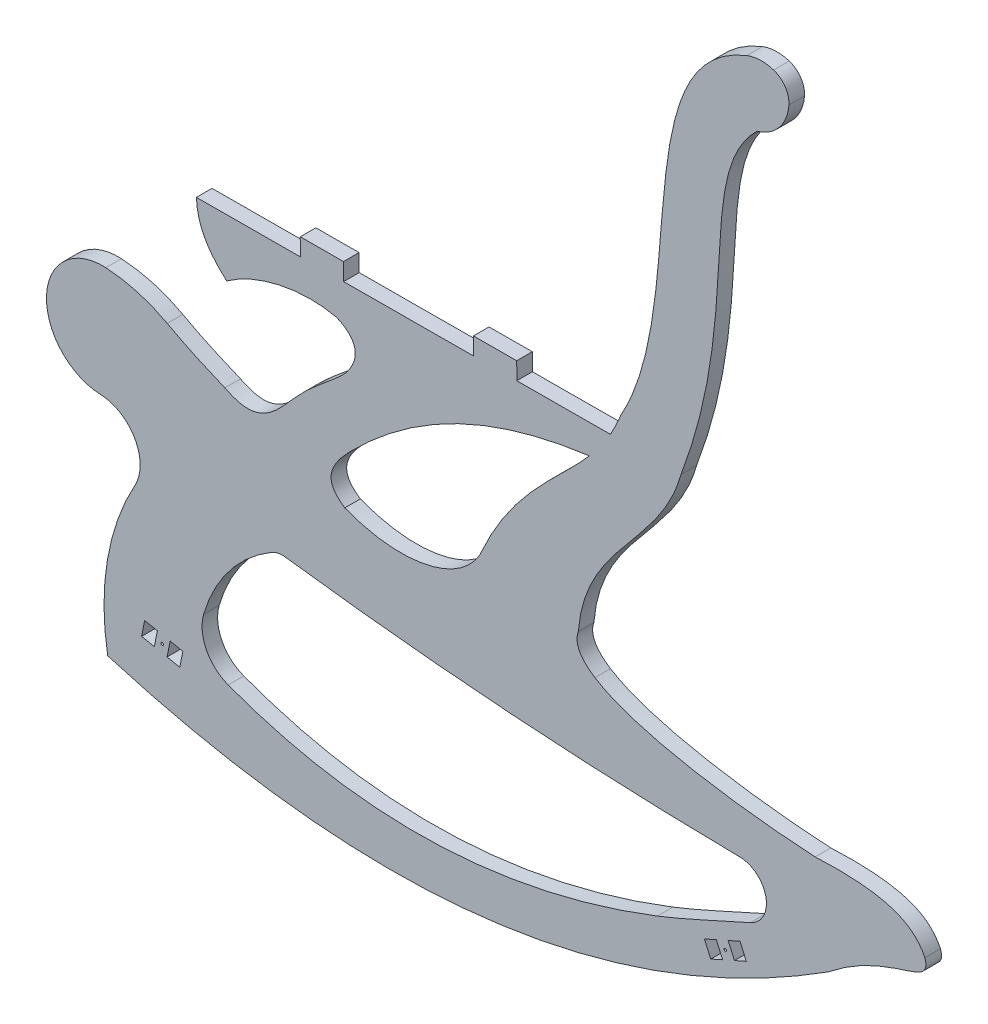
SolidWorks part; units mm, degrees
material "Teak"
ref_plane "Front Plane" through (0, 0, 0) normal (0, 0, 1) x (1, 0, 0)
ref_plane "Top Plane" through (0, 0, 0) normal (0, 1, 0) x (1, 0, 0)
ref_plane "Right Plane" through (0, 0, 0) normal (1, 0, 0) x (0, 0, -1)
sketch "Несущая боковая" plane through (0, 0, 0) normal (0, 0, 1) x (1, 0, 0)
  line L6 (398.785, -200.6515) -> (-79.2948, -202.7)
  arc A0 (568.0858, 187.1743) -> (604.9253, 231.748) centre (555.0835, 235.431) ccw
  arc A1 (604.9253, 231.748) -> (587.3016, 257.9076) centre (579.4885, 233.6276) ccw
  arc A2 (587.3016, 257.9076) -> (556.344, 256.9224) centre (573.2016, 214.0906) ccw
  arc A4 (-150.2921, -526.2545) -> (-190.0816, -455.2016) centre (-192.0175, -502.9531) ccw
  arc A7 (-150.2921, -526.2545) -> (-181.6944, -712.4375) centre (95.3308, -663.4217) ccw
  arc A8 (-183.8786, -325.353) -> (-190.0816, -455.2016) centre (-187.4487, -390.2549) ccw
  arc A9 (-112.9747, -345.6094) -> (-183.8786, -325.353) centre (-193.0224, -491.581) ccw
  arc A10 (560.3467, -608.2215) -> (548.1989, -548.57) centre (547.8281, -579.7082) ccw
  arc A11 (23.5507, -511.1423) -> (548.1989, -548.57) centre (601.0308, 3887.8918) ccw
  arc A12 (7.2112, -514.4863) -> (-70.9864, -615.6156) centre (95.3308, -663.4217) ccw
  arc A13 (-70.9864, -615.6156) -> (-42.6063, -671.9817) centre (-26.3207, -628.4543) ccw
  arc A14 (23.5507, -511.1423) -> (7.2112, -514.4863) centre (20.2245, -536.4807) ccw
  spline S0 degree 3 poles (556.344, 256.9224) (413.4931, 200.7) (492.8039, -30.4464) (410.7267, -175.5993) knots 0.000401 0.000401 0.000401 0.000401 0.043478 0.043478 0.043478 0.043478
  spline S1 degree 3 poles (410.7267, -175.5993) (407.231, -184.6492) (403.2193, -192.9282) (398.785, -200.6515) knots 0.043478 0.043478 0.043478 0.043478 0.086957 0.086957 0.086957 0.086957
  spline S2 degree 3 poles (-79.2948, -202.7) (-78.5172, -227.7) (-66.7741, -249.7094) (-44.1772, -268.7587) knots 0.130435 0.130435 0.130435 0.130435 0.173913 0.173913 0.173913 0.173913
  spline S3 degree 3 poles (-44.1772, -268.7587) (-12.7058, -245.829) (38.9597, -231.7344) (82.6666, -241.804) knots 0.173913 0.173913 0.173913 0.173913 0.217391 0.217391 0.217391 0.217391
  spline S4 degree 3 poles (82.6666, -241.804) (105.6787, -251.6525) (111.2464, -268.6919) (94.2115, -290.7234) knots 0.217391 0.217391 0.217391 0.217391 0.26087 0.26087 0.26087 0.26087
  spline S5 degree 3 poles (94.2115, -290.7234) (87.1581, -299.8457) (74.9831, -308.4217) (61.0599, -320.5021) knots 0.26087 0.26087 0.26087 0.26087 0.304348 0.304348 0.304348 0.304348
  spline S6 degree 3 poles (61.0599, -320.5021) (47.3806, -331.8412) (34.8832, -345.2678) (22.8705, -359.1067) knots 0.304348 0.304348 0.304348 0.304348 0.347826 0.347826 0.347826 0.347826
  spline S7 degree 3 poles (22.8705, -359.1067) (-5.5844, -391.8897) (-25.5922, -386.6363) (-46.4172, -376.7876) knots 0.347826 0.347826 0.347826 0.347826 0.391304 0.391304 0.391304 0.391304
  spline S8 degree 3 poles (-46.4172, -376.7876) (-71.9902, -366.2219) (-92.784, -356.6815) (-112.9747, -345.6094) knots 0.391304 0.391304 0.391304 0.391304 0.434783 0.434783 0.434783 0.434783
  spline S14 degree 3 poles (-181.6944, -712.4375) (138.4622, -807.7317) (410.6911, -765.399) (650.1904, -612.5982) knots 0.652174 0.652174 0.652174 0.652174 0.695652 0.695652 0.695652 0.695652
  spline S15 degree 3 poles (650.1904, -612.5982) (721.7263, -555.1366) (771.3742, -572.8028) (761.971, -542.4383) knots 0.695652 0.695652 0.695652 0.695652 0.73913 0.73913 0.73913 0.73913
  spline S16 degree 3 poles (761.971, -542.4383) (749.9881, -518.2511) (723.1034, -500.8362) (635.2399, -505.0064) knots 0.73913 0.73913 0.73913 0.73913 0.782609 0.782609 0.782609 0.782609
  spline S17 degree 3 poles (635.2399, -505.0064) (572.992, -501.9328) (433.5503, -486.7788) (380.9104, -452.9037) knots 0.782609 0.782609 0.782609 0.782609 0.826087 0.826087 0.826087 0.826087
  spline S18 degree 3 poles (380.9104, -452.9037) (364.7659, -442.5143) (356.7862, -430.3638) (361.7026, -416.2609) knots 0.826087 0.826087 0.826087 0.826087 0.869565 0.869565 0.869565 0.869565
  spline S19 degree 3 poles (361.7026, -416.2609) (369.7577, -319.5618) (455.7474, -287.137) (480.2427, -200.3025) knots 0.869565 0.869565 0.869565 0.869565 0.913043 0.913043 0.913043 0.913043
  spline S20 degree 3 poles (480.2427, -200.3025) (553.5443, -5.6015) (495.01, 115.2768) (568.0858, 187.1743) knots 0.913043 0.913043 0.913043 0.913043 0.956522 0.956522 0.956522 0.956522
  spline S25 degree 3 poles (452.9574, -655.3702) (274.7112, -724.495) (109.7393, -728.981) (-42.6063, -671.9817) knots 0.555556 0.555556 0.555556 0.555556 0.666667 0.666667 0.666667 0.666667
  spline S26 degree 3 poles (560.3467, -608.2215) (524.5503, -623.9377) (490.7002, -640.4881) (452.9574, -655.3702) knots 0.444444 0.444444 0.444444 0.444444 0.555556 0.555556 0.555556 0.555556
  spline S31 degree 3 poles (97.4618, -368.9486) (168.6207, -296.3511) (255.442, -250.0892) (374.5085, -234.3308) knots 0.75 0.75 0.75 0.75 1 1 1 1
  spline S32 degree 3 poles (92.0908, -427.5464) (69.7947, -412.5311) (70.4905, -396.4567) (97.4618, -368.9486) knots 0.5 0.5 0.5 0.5 0.75 0.75 0.75 0.75
  spline S33 degree 3 poles (247.8827, -396.6458) (222.4754, -441.0979) (152.6914, -451.7196) (92.0908, -427.5464) knots 0.25 0.25 0.25 0.25 0.5 0.5 0.5 0.5
  spline S34 degree 3 poles (374.5085, -234.3308) (336.7044, -278.0035) (285.6362, -310.9643) (247.8827, -396.6458) knots 0 0 0 0 0.25 0.25 0.25 0.25
  dimension "D2" = 65
sketch "Боковая под поперечины" plane through (0, 0, 0) normal (0, 0, 1) x (1, 0, 0)
  line L15 (-159.6049, -346.9107) -> (-207.6507, -344.8161) construction
  line L16 (-207.6507, -344.8161) -> (-235.0021, -434.5683)
  line L56 (-207.6507, -344.8161) -> (-159.6963, -346.9068)
  line L57 (-159.6963, -346.9068) -> (-148.2015, -350.3521)
  line L58 (-148.2015, -350.3521) -> (-104.2437, -369.6319)
  line L59 (-104.2437, -369.6319) -> (-95.353, -374.2095)
  line L60 (-95.353, -374.2095) -> (-51.5894, -393.9261)
  line L61 (-51.5894, -393.9261) -> (-42.3459, -397.7417)
  line L62 (-42.3459, -397.7417) -> (2.1537, -415.7357)
  line L63 (2.1537, -415.7357) -> (11.4455, -419.432)
  line L64 (11.4455, -419.432) -> (56.3986, -436.2612)
  line L65 (56.3986, -436.2612) -> (65.8381, -439.5619)
  line L66 (65.8381, -439.5619) -> (111.7403, -453.5971)
  line L67 (111.7403, -453.5971) -> (121.3499, -456.3643)
  line L68 (121.3499, -456.3643) -> (169.2689, -459.1514)
  line L69 (169.2689, -459.1514) -> (179.2066, -458.0374)
  line L70 (179.2066, -458.0374) -> (224.5179, -442.198)
  line L71 (224.5179, -442.198) -> (232.8956, -436.7378)
  line L72 (232.8956, -436.7378) -> (261.7321, -398.3651)
  line L73 (261.7321, -398.3651) -> (267.2053, -389.9959)
  line L74 (267.2053, -389.9959) -> (294.9373, -350.8177)
  line L75 (294.9373, -350.8177) -> (300.8954, -342.7864)
  line L76 (300.8954, -342.7864) -> (330.585, -305.0699)
  line L77 (330.585, -305.0699) -> (336.9867, -297.3877)
  line L78 (336.9867, -297.3877) -> (368.9263, -261.5566)
  line L79 (368.9263, -261.5566) -> (376.1332, -254.6241)
  line L80 (376.1332, -254.6241) -> (406.9239, -217.801)
  line L81 (406.9239, -217.801) -> (412.4436, -209.4624)
  line L82 (412.4436, -209.4624) -> (434.4129, -166.7851)
  line L83 (438.0837, -157.4832) -> (452.6073, -111.7332)
  line L84 (452.6073, -111.7332) -> (454.9033, -102.0003)
  line L85 (454.9033, -102.0003) -> (464.25, -54.9191)
  line L86 (464.25, -54.9191) -> (465.6878, -45.023)
  line L87 (465.6878, -45.023) -> (472.014, 2.5582)
  line L88 (472.014, 2.5582) -> (473.0512, 12.5043)
  line L89 (473.0512, 12.5043) -> (478.3742, 60.2082)
  line L90 (478.3742, 60.2082) -> (479.4656, 70.1485)
  line L91 (479.4656, 70.1485) -> (486.2184, 117.6711)
  line L92 (486.2184, 117.6711) -> (487.9962, 127.5118)
  line L93 (487.9962, 127.5118) -> (500.2801, 173.9134)
  line L94 (500.2801, 173.9134) -> (504.8877, 188.1882)
  line L95 (504.8877, 188.1882) -> (532.6089, 227.3741)
  line L96 (532.6089, 227.3741) -> (546.1164, 235.9502)
  line L97 (546.1164, 235.9502) -> (589.1375, 257.2382)
  line L99 (434.4129, -166.7851) -> (438.0837, -157.4832)
  arc A4 (568.0858, 187.1743) -> (604.9253, 231.748) centre (554.9668, 235.5274) ccw
  arc A7 (604.9253, 231.748) -> (589.1375, 257.2382) centre (579.4223, 233.5866) ccw
  arc A10 (604.9253, 231.748) -> (587.3016, 257.9076) centre (579.4885, 233.6276) ccw construction
  arc A11 (-144.8294, -495.3868) -> (-22.9392, -537.0926) centre (-72.7974, -483.8369) ccw
  arc A12 (7.2112, -514.4863) -> (-22.9392, -537.0926) centre (95.3308, -663.4217) ccw
  arc A13 (23.5507, -511.1423) -> (7.2112, -514.4863) centre (20.2245, -536.4807) ccw
  arc A15 (-144.8294, -495.3868) -> (-190.0816, -455.2016) centre (-192.0175, -502.9531) ccw
  arc A16 (23.5507, -511.1423) -> (352.014, -541.8909) centre (601.0308, 3887.8918) ccw
  arc A17 (-150.2921, -526.2545) -> (-190.0816, -455.2016) centre (-192.0175, -502.9531) ccw construction
  arc A18 (-183.8786, -325.353) -> (-190.0816, -455.2016) centre (-187.4487, -390.2549) ccw construction
  arc A19 (-235.0021, -434.5683) -> (-190.0816, -455.2016) centre (-187.4487, -390.2549) ccw
  arc A20 (23.5507, -511.1423) -> (548.1989, -548.57) centre (601.0308, 3887.8918) ccw construction
  arc A21 (23.5507, -511.1423) -> (7.2112, -514.4863) centre (20.2245, -536.4807) ccw construction
  arc A22 (7.2112, -514.4863) -> (-70.9864, -615.6156) centre (95.3308, -663.4217) ccw construction
  arc A23 (352.014, -541.8909) -> (380.9104, -452.9037) centre (354.7294, -493.5874) ccw
  spline S13 degree 3 poles (380.9104, -452.9037) (364.7659, -442.5143) (356.7861, -430.3638) (361.7026, -416.2609) knots 0.5 0.5 0.5 0.5 0.533333 0.533333 0.533333 0.533333
  spline S14 degree 3 poles (361.7026, -416.2609) (369.7577, -319.5618) (455.7474, -287.137) (480.2427, -200.3025) knots 0.533333 0.533333 0.533333 0.533333 0.566667 0.566667 0.566667 0.566667
  spline S15 degree 3 poles (480.2427, -200.3025) (553.5444, -5.6014) (495.0101, 115.2768) (568.0858, 187.1743) knots 0.566667 0.566667 0.566667 0.566667 0.6 0.6 0.6 0.6
  point P66 (608.2751, 264.1653)
  point P67 (553.7309, 240.2756)
  point P74 (-221.3236, -344.22)
  dimension "D1" = 48
  dimension "D2" = 12
  dimension "D3" = 10
  dimension "D10" = 16
  dimension "D11" = 15
extrude "Несущая" add sketch "Несущая боковая" along normal blind 18
extrude "Боковая" [suppressed] add sketch "Боковая под поперечины" along normal blind 21
sketch "Sketch3" [suppressed] plane through (0, 0, 0) normal (0, 0, 1) x (1, 0, 0)
  line L0 (546.1164, 235.9502) -> (589.1375, 257.2382) construction
  line L2 (-213.1197, -424.5103) -> (-208.4556, -409.2052) construction
  line L3 (-230.338, -419.2632) -> (-225.6738, -403.9581) construction
  line L4 (-208.4556, -409.2052) -> (-203.7915, -393.9001)
  line L6 (-230.338, -419.2632) -> (-213.1197, -424.5103)
  line L10 (-207.6507, -344.8161) -> (-191.6659, -345.513)
  line L11 (-207.6507, -344.8161) -> (-208.4348, -362.799)
  line L12 (-159.6963, -346.9068) -> (-160.4803, -364.8897)
  line L13 (-208.4348, -362.799) -> (-192.4499, -363.4959)
  line L14 (-191.6659, -345.513) -> (-192.4499, -363.4959)
  line L15 (-175.6811, -346.2099) -> (-176.4651, -364.1928)
  line L16 (-176.4651, -364.1928) -> (-160.4803, -364.8897)
  line L17 (-192.4499, -363.4959) -> (-176.4651, -364.1928) construction
  line L18 (-175.6811, -346.2099) -> (-159.6963, -346.9068)
  line L19 (-191.6659, -345.513) -> (-175.6811, -346.2099) construction
  line L37 (-133.5489, -356.7787) -> (-140.7788, -373.2629)
  line L38 (-118.8963, -363.2053) -> (-126.1262, -379.6895)
  line L40 (-155.4315, -366.8363) -> (-140.7788, -373.2629)
  line L41 (-118.8963, -363.2053) -> (-104.2437, -369.6319)
  line L42 (-140.7788, -373.2629) -> (-126.1262, -379.6895) construction
  line L43 (-104.2437, -369.6319) -> (-111.4736, -386.1161)
  line L44 (-126.1262, -379.6895) -> (-111.4736, -386.1161)
  line L45 (-148.2015, -350.3521) -> (-133.5489, -356.7787)
  line L46 (-133.5489, -356.7787) -> (-118.8963, -363.2053) construction
  line L47 (-148.2015, -350.3521) -> (-155.4315, -366.8363)
  line L48 (-104.2437, -369.6319) -> (-148.2015, -350.3521) construction
  line L49 (-66.1772, -387.3539) -> (-73.571, -403.7653)
  line L50 (-80.7651, -380.7817) -> (-66.1772, -387.3539) construction
  line L51 (-80.7651, -380.7817) -> (-88.1588, -397.1931)
  line L52 (-66.1772, -387.3539) -> (-51.5894, -393.9261)
  line L53 (-102.7467, -390.6208) -> (-88.1588, -397.1931)
  line L54 (-51.5894, -393.9261) -> (-58.9831, -410.3375)
  line L55 (-95.353, -374.2095) -> (-80.7651, -380.7817)
  line L56 (-88.1588, -397.1931) -> (-73.571, -403.7653) construction
  line L57 (-73.571, -403.7653) -> (-58.9831, -410.3375)
  line L58 (-95.353, -374.2095) -> (-102.7467, -390.6208)
  line L59 (-34.2604, -420.427) -> (-19.4272, -426.425) construction
  line L60 (-27.5127, -403.7397) -> (-12.6795, -409.7377) construction
  line L61 (-42.3459, -397.7417) -> (-27.5127, -403.7397)
  line L62 (-12.6795, -409.7377) -> (2.1537, -415.7357)
  line L63 (-49.0936, -414.429) -> (-34.2604, -420.427)
  line L64 (-12.6795, -409.7377) -> (-19.4272, -426.425)
  line L65 (-42.3459, -397.7417) -> (-49.0936, -414.429)
  line L66 (-19.4272, -426.425) -> (-4.594, -432.423)
  line L67 (-27.5127, -403.7397) -> (-34.2604, -420.427)
  line L68 (2.1537, -415.7357) -> (-4.594, -432.423)
  line L69 (41.4142, -430.6515) -> (35.1033, -447.5089)
  line L70 (56.3986, -436.2612) -> (50.0876, -453.1186)
  line L71 (26.4299, -425.0417) -> (41.4142, -430.6515) construction
  line L72 (26.4299, -425.0417) -> (20.1189, -441.8991)
  line L73 (5.1346, -436.2894) -> (20.1189, -441.8991)
  line L74 (11.4455, -419.432) -> (26.4299, -425.0417)
  line L75 (41.4142, -430.6515) -> (56.3986, -436.2612)
  line L76 (11.4455, -419.432) -> (5.1346, -436.2894)
  line L77 (35.1033, -447.5089) -> (50.0876, -453.1186)
  line L78 (20.1189, -441.8991) -> (35.1033, -447.5089) construction
  line L79 (91.1764, -466.1321) -> (106.4771, -470.8105)
  line L80 (65.8381, -439.5619) -> (60.5749, -456.7753)
  line L81 (96.4396, -448.9187) -> (91.1764, -466.1321)
  line L82 (81.1389, -444.2403) -> (75.8757, -461.4537)
  line L83 (65.8381, -439.5619) -> (81.1389, -444.2403)
  line L84 (60.5749, -456.7753) -> (75.8757, -461.4537)
  line L85 (96.4396, -448.9187) -> (111.7403, -453.5971)
  line L86 (111.7403, -453.5971) -> (106.4771, -470.8105)
  line L87 (75.8757, -461.4537) -> (91.1764, -466.1321) construction
  line L88 (81.1389, -444.2403) -> (96.4396, -448.9187) construction
  line L89 (120.3047, -474.3339) -> (136.2777, -475.263)
  line L90 (153.2959, -458.2223) -> (169.2689, -459.1514)
  line L91 (136.2777, -475.263) -> (152.2507, -476.192) construction
  line L92 (153.2959, -458.2223) -> (152.2507, -476.192)
  line L93 (152.2507, -476.192) -> (168.2237, -477.121)
  line L94 (121.3499, -456.3643) -> (137.3229, -457.2933)
  line L95 (137.3229, -457.2933) -> (153.2959, -458.2223) construction
  line L96 (121.3499, -456.3643) -> (120.3047, -474.3339)
  line L97 (137.3229, -457.2933) -> (136.2777, -475.263)
  line L98 (169.2689, -459.1514) -> (168.2237, -477.121)
  line L99 (215.3539, -464.4695) -> (230.4577, -459.1897)
  line L100 (194.3104, -452.7576) -> (209.4142, -447.4778) construction
  line L101 (194.3104, -452.7576) -> (200.2502, -469.7493)
  line L102 (185.1464, -475.0291) -> (200.2502, -469.7493)
  line L103 (224.5179, -442.198) -> (230.4577, -459.1897)
  line L104 (200.2502, -469.7493) -> (215.3539, -464.4695) construction
  line L105 (179.2066, -458.0374) -> (185.1464, -475.0291)
  line L106 (209.4142, -447.4778) -> (224.5179, -442.198)
  line L107 (179.2066, -458.0374) -> (194.3104, -452.7576)
  line L108 (209.4142, -447.4778) -> (215.3539, -464.4695)
  line L109 (256.8975, -434.7606) -> (266.5097, -421.9697) construction
  line L110 (266.5097, -421.9697) -> (276.1219, -409.1788)
  line L111 (247.2854, -447.5514) -> (256.8975, -434.7606)
  line L112 (242.5078, -423.9469) -> (256.8975, -434.7606)
  line L113 (252.12, -411.156) -> (261.7321, -398.3651)
  line L114 (261.7321, -398.3651) -> (276.1219, -409.1788)
  line L115 (232.8956, -436.7378) -> (242.5078, -423.9469)
  line L116 (242.5078, -423.9469) -> (252.12, -411.156) construction
  line L117 (232.8956, -436.7378) -> (247.2854, -447.5514)
  line L118 (252.12, -411.156) -> (266.5097, -421.9697)
  line L119 (267.2053, -389.9959) -> (276.4493, -376.9365)
  line L120 (267.2053, -389.9959) -> (281.8971, -400.3954)
  line L121 (281.8971, -400.3954) -> (291.1411, -387.336)
  line L122 (276.4493, -376.9365) -> (291.1411, -387.336)
  line L123 (291.1411, -387.336) -> (300.3852, -374.2766) construction
  line L124 (285.6933, -363.8771) -> (300.3852, -374.2766)
  line L125 (294.9373, -350.8177) -> (309.6292, -361.2172)
  line L126 (300.3852, -374.2766) -> (309.6292, -361.2172)
  line L127 (285.6933, -363.8771) -> (294.9373, -350.8177)
  line L128 (276.4493, -376.9365) -> (285.6933, -363.8771) construction
  line L129 (334.8321, -328.7757) -> (344.7286, -316.2035)
  line L130 (324.9356, -341.3478) -> (334.8321, -328.7757) construction
  line L131 (310.7919, -330.2143) -> (320.6885, -317.6421) construction
  line L132 (300.8954, -342.7864) -> (310.7919, -330.2143)
  line L133 (300.8954, -342.7864) -> (315.0391, -353.92)
  line L134 (310.7919, -330.2143) -> (324.9356, -341.3478)
  line L135 (320.6885, -317.6421) -> (334.8321, -328.7757)
  line L136 (315.0391, -353.92) -> (324.9356, -341.3478)
  line L137 (330.585, -305.0699) -> (344.7286, -316.2035)
  line L138 (320.6885, -317.6421) -> (330.585, -305.0699)
  line L139 (336.9867, -297.3877) -> (350.4234, -309.365)
  line L140 (358.2798, -273.5003) -> (371.7164, -285.4777)
  line L141 (371.7164, -285.4777) -> (382.363, -273.534)
  line L142 (350.4234, -309.365) -> (361.0699, -297.4213)
  line L143 (361.0699, -297.4213) -> (371.7164, -285.4777) construction
  line L144 (336.9867, -297.3877) -> (347.6333, -285.444)
  line L145 (368.9263, -261.5566) -> (382.363, -273.534)
  line L146 (358.2798, -273.5003) -> (368.9263, -261.5566)
  line L147 (347.6333, -285.444) -> (358.2798, -273.5003) construction
  line L148 (347.6333, -285.444) -> (361.0699, -297.4213)
  line L149 (410.469, -241.6218) -> (420.7325, -229.3475)
  line L150 (396.6603, -230.0754) -> (410.469, -241.6218)
  line L151 (400.2054, -253.8962) -> (410.469, -241.6218) construction
  line L152 (389.9419, -266.1706) -> (400.2054, -253.8962)
  line L153 (406.9239, -217.801) -> (420.7325, -229.3475)
  line L154 (376.1332, -254.6241) -> (386.3968, -242.3497)
  line L155 (376.1332, -254.6241) -> (389.9419, -266.1706)
  line L156 (396.6603, -230.0754) -> (406.9239, -217.801)
  line L157 (386.3968, -242.3497) -> (400.2054, -253.8962)
  line L158 (386.3968, -242.3497) -> (396.6603, -230.0754) construction
  line L159 (443.0938, -189.2494) -> (450.4169, -175.0237)
  line L160 (427.0898, -181.0109) -> (434.4129, -166.7851)
  line L161 (427.0898, -181.0109) -> (443.0938, -189.2494)
  line L162 (419.7667, -195.2366) -> (435.7706, -203.4751)
  line L163 (435.7706, -203.4751) -> (443.0938, -189.2494) construction
  line L164 (412.4436, -209.4624) -> (428.4475, -217.7009)
  line L165 (428.4475, -217.7009) -> (435.7706, -203.4751)
  line L166 (434.4129, -166.7851) -> (450.4169, -175.0237)
  line L167 (419.7667, -195.2366) -> (427.0898, -181.0109) construction
  line L168 (412.4436, -209.4624) -> (419.7667, -195.2366)
  line L169 (455.24, -162.9296) -> (460.0811, -147.6795)
  line L170 (447.7661, -126.9832) -> (452.6073, -111.7332)
  line L171 (442.9249, -142.2332) -> (460.0811, -147.6795)
  line L172 (447.7661, -126.9832) -> (464.9223, -132.4295)
  line L173 (438.0837, -157.4832) -> (442.9249, -142.2332)
  line L174 (464.9223, -132.4295) -> (469.7635, -117.1795)
  line L175 (442.9249, -142.2332) -> (447.7661, -126.9832) construction
  line L176 (452.6073, -111.7332) -> (469.7635, -117.1795)
  line L177 (438.0837, -157.4832) -> (455.24, -162.9296)
  line L178 (460.0811, -147.6795) -> (464.9223, -132.4295) construction
  line L179 (-51.5894, -393.9261) -> (-95.353, -374.2095) construction
  line L180 (2.1537, -415.7357) -> (-42.3459, -397.7417) construction
  line L181 (56.3986, -436.2612) -> (11.4455, -419.432) construction
  line L182 (368.9263, -261.5566) -> (336.9867, -297.3877) construction
  line L183 (406.9239, -217.801) -> (376.1332, -254.6241) construction
  line L184 (434.4129, -166.7851) -> (412.4436, -209.4624) construction
  line L185 (452.6073, -111.7332) -> (438.0837, -157.4832) construction
  line L186 (472.5587, -105.5054) -> (475.6743, -89.8116)
  line L187 (458.0188, -86.3066) -> (461.1344, -70.6129) construction
  line L188 (454.9033, -102.0003) -> (458.0188, -86.3066)
  line L189 (458.0188, -86.3066) -> (475.6743, -89.8116)
  line L190 (461.1344, -70.6129) -> (464.25, -54.9191)
  line L191 (454.9033, -102.0003) -> (472.5587, -105.5054)
  line L192 (464.25, -54.9191) -> (481.9054, -58.4242)
  line L193 (475.6743, -89.8116) -> (478.7898, -74.1179) construction
  line L194 (461.1344, -70.6129) -> (478.7898, -74.1179)
  line L195 (478.7898, -74.1179) -> (481.9054, -58.4242)
  line L196 (467.7965, -29.1626) -> (469.9053, -13.3022) construction
  line L197 (465.6878, -45.023) -> (467.7965, -29.1626)
  line L198 (472.014, 2.5582) -> (489.857, 0.1859)
  line L199 (485.6395, -31.5349) -> (487.7482, -15.6745) construction
  line L200 (469.9053, -13.3022) -> (472.014, 2.5582)
  line L201 (487.7482, -15.6745) -> (489.857, 0.1859)
  line L202 (465.6878, -45.023) -> (483.5308, -47.3954)
  line L203 (467.7965, -29.1626) -> (485.6395, -31.5349)
  line L204 (469.9053, -13.3022) -> (487.7482, -15.6745)
  line L205 (483.5308, -47.3954) -> (485.6395, -31.5349)
  line L206 (473.0512, 12.5043) -> (474.8255, 28.4056)
  line L207 (474.8255, 28.4056) -> (476.5998, 44.3069) construction
  line L208 (473.0512, 12.5043) -> (490.9401, 10.5082)
  line L209 (494.4888, 42.3108) -> (496.2632, 58.2121)
  line L210 (476.5998, 44.3069) -> (494.4888, 42.3108)
  line L211 (474.8255, 28.4056) -> (492.7145, 26.4095)
  line L212 (490.9401, 10.5082) -> (492.7145, 26.4095)
  line L213 (492.7145, 26.4095) -> (494.4888, 42.3108) construction
  line L214 (478.3742, 60.2082) -> (496.2632, 58.2121)
  line L215 (476.5998, 44.3069) -> (478.3742, 60.2082)
  line L216 (486.2184, 117.6711) -> (504.0394, 115.1388)
  line L217 (481.7165, 85.9894) -> (483.9675, 101.8303) construction
  line L218 (499.5375, 83.4571) -> (501.7885, 99.2979) construction
  line L219 (501.7885, 99.2979) -> (504.0394, 115.1388)
  line L220 (483.9675, 101.8303) -> (486.2184, 117.6711)
  line L221 (483.9675, 101.8303) -> (501.7885, 99.2979)
  line L222 (479.4656, 70.1485) -> (481.7165, 85.9894)
  line L223 (479.4656, 70.1485) -> (497.2865, 67.6162)
  line L224 (481.7165, 85.9894) -> (499.5375, 83.4571)
  line L225 (497.2865, 67.6162) -> (499.5375, 83.4571)
  line L226 (500.2801, 173.9134) -> (517.6807, 169.307)
  line L227 (505.3968, 122.9054) -> (509.4914, 138.3726)
  line L228 (492.0908, 142.979) -> (496.1855, 158.4462) construction
  line L229 (513.5861, 153.8398) -> (517.6807, 169.307)
  line L230 (487.9962, 127.5118) -> (492.0908, 142.979)
  line L231 (487.9962, 127.5118) -> (505.3968, 122.9054)
  line L232 (492.0908, 142.979) -> (509.4914, 138.3726)
  line L233 (496.1855, 158.4462) -> (513.5861, 153.8398)
  line L234 (509.4914, 138.3726) -> (513.5861, 153.8398) construction
  line L235 (496.1855, 158.4462) -> (500.2801, 173.9134)
  line L236 (514.1281, 201.2502) -> (523.3685, 214.3121) construction
  line L237 (504.8877, 188.1882) -> (519.5824, 177.7928)
  line L238 (523.3685, 214.3121) -> (532.6089, 227.3741)
  line L239 (514.1281, 201.2502) -> (528.8228, 190.8547)
  line L240 (523.3685, 214.3121) -> (538.0632, 203.9167)
  line L241 (532.6089, 227.3741) -> (547.3036, 216.9787)
  line L242 (504.8877, 188.1882) -> (514.1281, 201.2502)
  line L243 (538.0632, 203.9167) -> (547.3036, 216.9787)
  line L244 (519.5824, 177.7928) -> (528.8228, 190.8547)
  line L245 (528.8228, 190.8547) -> (538.0632, 203.9167) construction
  line L246 (589.1375, 257.2382) -> (597.1205, 241.1053)
  line L247 (560.4567, 243.0462) -> (568.4398, 226.9133)
  line L248 (546.1164, 235.9502) -> (560.4567, 243.0462)
  line L249 (574.7971, 250.1422) -> (582.7801, 234.0093)
  line L250 (582.7801, 234.0093) -> (597.1205, 241.1053)
  line L251 (560.4567, 243.0462) -> (574.7971, 250.1422) construction
  line L252 (546.1164, 235.9502) -> (554.0994, 219.8172)
  line L253 (568.4398, 226.9133) -> (582.7801, 234.0093) construction
  line L254 (574.7971, 250.1422) -> (589.1375, 257.2382)
  line L255 (554.0994, 219.8172) -> (568.4398, 226.9133)
  line L256 (464.25, -54.9191) -> (454.9033, -102.0003) construction
  line L257 (472.014, 2.5582) -> (465.6878, -45.023) construction
  line L258 (486.2184, 117.6711) -> (479.4656, 70.1485) construction
  line L259 (500.2801, 173.9134) -> (487.9962, 127.5118) construction
  line L260 (487.9962, 127.5118) -> (486.2184, 117.6711) construction
  line L261 (532.6089, 227.3741) -> (504.8877, 188.1882) construction
  line L262 (504.8877, 188.1882) -> (500.2801, 173.9134) construction
  line L263 (-217.7838, -439.8154) -> (-213.1197, -424.5103)
  line L264 (-225.6738, -403.9581) -> (-208.4556, -409.2052)
  line L265 (-221.0097, -388.653) -> (-203.7915, -393.9001)
  line L266 (-235.0021, -434.5683) -> (-217.7838, -439.8154)
  line L267 (-225.6738, -403.9581) -> (-221.0097, -388.653)
  line L268 (-235.0021, -434.5683) -> (-230.338, -419.2632)
  line L269 (-207.6507, -344.8161) -> (-235.0021, -434.5683) construction
  dimension "D2" = 18
  dimension "D3" = 16
extrude "Шипы" [suppressed] cut sketch "Sketch3" along normal through all
sketch "Sketch4" [suppressed] plane through (0, 0, 21) normal (0, 0, 1) x (1, 0, 0)
  line L0 (-208.4348, -362.799) -> (-221.0097, -388.653)
  line L1 (-221.0097, -388.653) -> (-207.6507, -344.8161)
  line L2 (-207.6507, -344.8161) -> (-208.4348, -362.799)
  line L3 (-217.7838, -439.8154) -> (-213.1197, -424.5103) construction
  line L4 (-217.7838, -439.8154) -> (-237.4507, -429.7729)
  line L5 (-237.4507, -429.7729) -> (-240.164, -452.0896)
  line L6 (-240.164, -452.0896) -> (-213.0497, -450.0009)
  arc A0 (-217.7838, -439.8154) -> (-213.0497, -450.0009) centre (-209.7362, -442.2679) ccw
  arc A1 (-235.0021, -434.5683) -> (-190.0816, -455.2016) centre (-187.4487, -390.2549) ccw construction
extrude "Излишки" [suppressed] cut sketch "Sketch4" against normal up to next
sketch "Sketch5" plane through (0, 0, 18) normal (0, 0, 1) x (1, 0, 0)
  line L1 (40.6184, -182.186) -> (90.618, -181.9718)
  line L2 (40.6184, -182.186) -> (40.7041, -202.1858)
  line L3 (40.7041, -202.1858) -> (90.7037, -201.9716)
  line L4 (90.618, -181.9718) -> (90.7037, -201.9716)
  line L5 (398.785, -200.6515) -> (-79.2948, -202.7) construction
  line L6 (240.6166, -181.329) -> (290.6161, -181.1148)
  line L7 (240.6166, -181.329) -> (240.7023, -201.3289)
  line L8 (240.7023, -201.3289) -> (290.7018, -201.1146)
  line L9 (290.6161, -181.1148) -> (290.7018, -201.1146)
  dimension "D1" = 20
  dimension "D2" = 150
  dimension "D3" = 120
  dimension "D4" = 50
extrude "Шипы на подлокотниках" add sketch "Sketch5" against normal up to surface (18 mm away) up to face at (168.5307, -593.8353, 0)
sketch "Sketch6" plane through (0, 0, 18) normal (0, 0, 1) x (1, 0, 0)
  line L0 (-139.0626, -655.7461) -> (-142.5889, -673.3973)
  line L1 (-142.5889, -673.3973) -> (-127.8796, -676.3359)
  line L2 (-127.8796, -676.3359) -> (-124.3533, -658.6847)
  line L3 (-124.3533, -658.6847) -> (-139.0626, -655.7461)
  line L4 (-127.8796, -676.3359) -> (-113.1702, -679.2745) construction
  line L5 (-113.1702, -679.2745) -> (-109.6439, -661.6232)
  line L6 (-109.6439, -661.6232) -> (-94.9346, -664.5618)
  line L7 (-94.9346, -664.5618) -> (-98.4609, -682.213)
  line L8 (-98.4609, -682.213) -> (-113.1702, -679.2745)
  line L9 (-120.5249, -677.8052) -> (-116.9986, -660.154) construction
  line L10 (-124.3533, -658.6847) -> (-109.6439, -661.6232) construction
  line L11 (-126.1164, -667.5103) -> (-111.4071, -670.4489) construction
  line L12 (521.0426, -644.9347) -> (534.7498, -638.8426) construction
  line L13 (555.7675, -649.1991) -> (542.0603, -655.2912)
  line L14 (535.2067, -658.3373) -> (527.8962, -641.8886) construction
  line L15 (521.0426, -644.9347) -> (507.3355, -651.0268)
  line L16 (514.646, -667.4754) -> (528.3531, -661.3833)
  line L17 (528.3531, -661.3833) -> (542.0603, -655.2912) construction
  line L18 (528.3531, -661.3833) -> (521.0426, -644.9347)
  line L19 (542.0603, -655.2912) -> (534.7498, -638.8426)
  line L20 (524.6979, -653.159) -> (538.4051, -647.0669) construction
  line L21 (548.457, -632.7505) -> (555.7675, -649.1991)
  line L22 (507.3355, -651.0268) -> (514.646, -667.4754)
  line L23 (534.7498, -638.8426) -> (548.457, -632.7505)
  circle A2 centre (531.5515, -650.113) radius 1.5
  circle A4 centre (-118.7618, -668.9796) radius 1.5
  dimension "D1" = 18
  dimension "D4" = 3
  dimension "D6" = 3
  dimension "D2" = 15
  dimension "D3" = 18
  dimension "D5" = 15
extrude "Под ребра жесткости" cut sketch "Sketch6" against normal up to next
sketch "Sketch7" [suppressed] plane through (0, 0, 21) normal (0, 0, 1) x (1, 0, 0)
  line L0 (567.6269, 246.5942) -> (583.0969, 215.468) construction
  line L1 (574.7971, 250.1422) -> (560.4567, 243.0462) construction
  circle A0 centre (583.0969, 215.468) radius 10 construction
  circle A1 centre (583.0969, 215.468) radius 4
  circle A2 centre (349.1273, -502.2927) radius 4
  circle A3 centre (-72.7974, -483.8369) radius 4
  arc A4 (348.0519, -561.0148) -> (380.9104, -452.9037) centre (349.1273, -502.2927) ccw construction
  arc A5 (-144.8294, -495.3868) -> (-22.9392, -537.0926) centre (-72.7974, -483.8369) ccw construction
  dimension "D1" = 8
  dimension "D2" = 20
extrude "Под болты М8" [suppressed] cut sketch "Sketch7" against normal blind 20
sketch "Sketch9" [suppressed] plane through (0, 0, 21) normal (0, 0, 1) x (1, 0, 0)
  circle A1 centre (-150.0179, -416.742) radius 1.5
  circle A2 centre (-19.0866, -469.5934) radius 1.5
  circle A3 centre (116.1327, -506.7832) radius 1.5
  circle A4 centre (265.4187, -506.7832) radius 1.5
  circle A5 centre (335.948, -380.5609) radius 1.5
  circle A6 centre (431.4673, -250.6533) radius 1.5
  circle A7 centre (486.9514, -124.9981) radius 1.5
  circle A8 centre (512.1042, 60.8892) radius 1.5
  dimension "D1" = 3
extrude "Под шурупы" [suppressed] cut sketch "Sketch9" against normal up to next
sketch "Sketch10" [suppressed] plane through (0, 0, 20) normal (0, 0, 1) x (1, 0, 0)
  circle A0 centre (-89.3655, -525.6855) radius 4
  circle A1 centre (349.1273, -502.2927) radius 4
  circle A2 centre (583.0969, 215.468) radius 4
  circle A3 centre (583.0969, 215.468) radius 4 construction
  circle A4 centre (349.1273, -502.2927) radius 4 construction
  circle A5 centre (-89.3655, -525.6855) radius 4 construction
extrude "Под болты М8 в несущей" [suppressed] cut sketch "Sketch10" against normal up to next
equation "\"mm\"=20"
